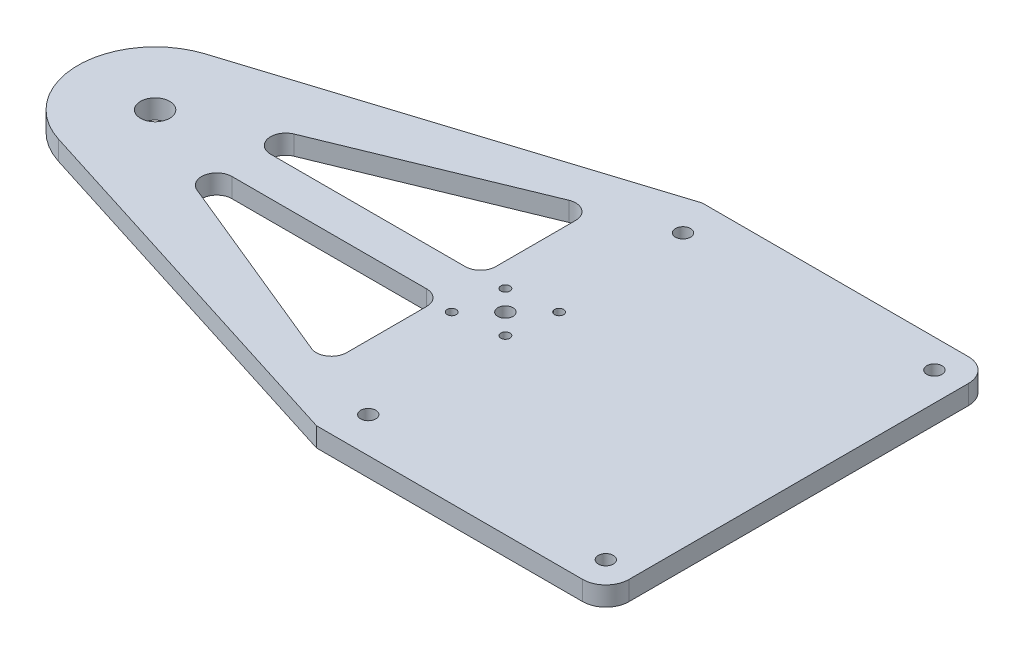
SolidWorks part; units mm, degrees
material "UHMW"
ref_plane "Front Plane" through (0, 0, 0) normal (0, 0, 1) x (1, 0, 0)
ref_plane "Top Plane" through (0, 0, 0) normal (0, 1, 0) x (1, 0, 0)
ref_plane "Right Plane" through (0, 0, 0) normal (1, 0, 0) x (0, 0, -1)
sketch "Sketch1" plane through (0, 0, 0) normal (0, 1, 0) x (1, 0, 0)
  line L0 (-47.625, 0) -> (47.625, 0) construction
  line L1 (-47.625, -63.5) -> (47.625, -63.5)
  line L2 (-47.625, -63.5) -> (-47.625, 63.5)
  line L3 (-47.625, 63.5) -> (47.625, 63.5)
  line L4 (47.625, -63.5) -> (47.625, 63.5)
  line L5 (-47.625, -63.5) -> (47.625, 63.5) construction
  line L6 (-47.625, 63.5) -> (47.625, -63.5) construction
  point P0 (0, 0)
  dimension "D1" = 95.25
  dimension "D2" = 127
  dimension "D3" = 63.5
extrude "Boss-Extrude1" add sketch "Sketch1" along normal blind 6.35
sketch "Sketch4" plane through (0, 6.35, 0) normal (0, 1, 0) x (1, 0, 0)
  line L1 (-47.625, 63.5) -> (-171.916, 24.2193)
  line L5 (-47.625, 63.5) -> (-47.625, -63.5) construction
  line L9 (-47.625, -63.5) -> (-171.916, -24.2193)
  line L10 (-47.625, 63.5) -> (-47.625, -63.5)
  arc A0 (-171.916, 24.2193) -> (-171.916, -24.2193) centre (-164.2618, 0) ccw
  circle A1 centre (-48.9458, 0) radius 2.5 construction
  dimension "D1" = 50.8
  dimension "D2" = 115.316
extrude "Boss-Extrude3" add sketch "Sketch4" against normal blind 6.35
sketch "Sketch5" plane through (0, 6.35, 0) normal (0, 1, 0) x (1, 0, 0)
  line L0 (-48.9458, 0) -> (-31.7264, 0) construction
  line L3 (-48.9458, 0) -> (-91.3931, 0) construction
  circle A0 centre (-164.2618, 0) radius 4.826
  circle A1 centre (-48.9458, 0) radius 2.5
  arc A2 (-171.916, 24.2193) -> (-171.916, -24.2193) centre (-164.2618, 0) ccw construction
  arc A3 (-171.916, 24.2193) -> (-171.916, -24.2193) centre (-164.2618, 0) ccw
  circle A4 centre (-42.2283, -6.7175) radius 1.5
  circle A5 centre (-40.107, 8.8388) radius 1.5
  circle A6 centre (-57.7846, -8.8388) radius 1.5
  circle A7 centre (-55.6633, 6.7175) radius 1.5
  circle A8 centre (-40.107, 8.8388) radius 1.5 construction
  circle A9 centre (-55.6633, 6.7175) radius 1.5 construction
  circle A10 centre (-57.7846, -8.8388) radius 1.5 construction
  circle A11 centre (-42.2283, -6.7175) radius 1.5 construction
  circle A12 centre (-48.9458, 0) radius 2.5 construction
  point P20 (-48.9458, 0)
  dimension "D1" = 9.652
extrude "Cut-Extrude1" cut sketch "Sketch5" against normal through all contours A0 | A1 | A5 | A6 | A7 | A4 region at (-164.2618, 6.35, 0) region at (-48.9458, 6.35, 0)
sketch "Sketch6" plane through (0, 6.35, 0) normal (0, 1, 0) x (1, 0, 0)
  line L0 (-63.5, 6.35) -> (-63.5, -6.35) construction
  line L1 (-63.5, 45.1637) -> (-157.9118, 6.35)
  line L2 (-157.9118, 6.35) -> (-63.5, 6.35)
  line L3 (-63.5, 6.35) -> (-63.5, 45.1637)
  line L4 (-63.5, -6.35) -> (-63.5, -45.1637)
  line L5 (-63.5, -45.1637) -> (-157.9118, -6.35)
  line L6 (-157.9118, -6.35) -> (-63.5, -6.35)
  line L7 (0, 0) -> (-63.5, 0) construction
  line L8 (-189.6618, 75.5498) -> (-189.6618, -75.5498) construction
  line L9 (-47.625, 63.5) -> (-171.916, 24.2193) construction
  arc A0 (-171.916, 24.2193) -> (-171.916, -24.2193) centre (-164.2618, 0) ccw construction
  point P12 (-189.6618, 0)
  dimension "D1" = 31.75
  dimension "D2" = 12.7
  dimension "D3" = 12.7
  dimension "D4" = 63.5
extrude "Cut-Extrude2" cut sketch "Sketch6" against normal through all
fillet "Fillet9" radius 5 6 edges at (-157.9118, 3.175, 6.35) (-63.5, 3.175, 6.35) (-63.5, 3.175, 45.1637) (-63.5, 3.175, -6.35) (-157.9118, 3.175, -6.35) (-63.5, 3.175, -45.1637)
fillet "Fillet10" radius 7.62 2 edges at (47.625, 3.175, -63.5) (47.625, 3.175, 63.5)
sketch "Sketch7" plane through (0, 6.35, 0) normal (0, 1, 0) x (1, 0, 0)
  circle A0 centre (-42.2861, -51.8111) radius 2.4892
  circle A1 centre (-42.2861, 51.8111) radius 2.4892
  circle A2 centre (38.2023, 54.0773) radius 2.4892
  circle A3 centre (38.2023, -54.0773) radius 2.4892
extrude "Cut-Extrude3" cut sketch "Sketch7" against normal through all
